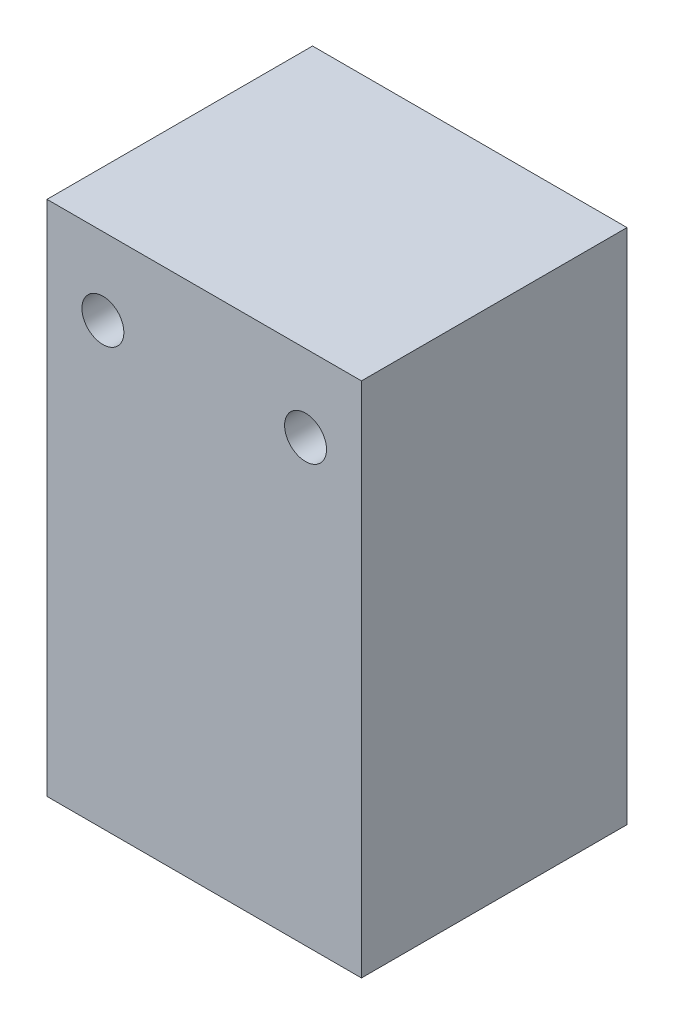
SolidWorks part; units mm, degrees
ref_plane "Front Plane" through (0, 0, 0) normal (0, 0, 1) x (1, 0, 0)
ref_plane "Top Plane" through (0, 0, 0) normal (0, 1, 0) x (1, 0, 0)
ref_plane "Right Plane" through (0, 0, 0) normal (1, 0, 0) x (0, 0, -1)
sketch "Sketch1" plane through (0, 0, 0) normal (0, 0, 1) x (1, 0, 0)
  line L0 (-11.25, 8.7) -> (-11.25, 0) construction
  line L1 (0, 0) -> (-22.5, 0)
  line L2 (0, 0) -> (0, 37)
  line L3 (0, 37) -> (-22.5, 37)
  line L4 (-22.5, 0) -> (-22.5, 37)
  line L5 (-13.0815, 8.7) -> (-9.4185, 8.7)
  line L7 (-13.0815, 12.4) -> (-9.4185, 12.4)
  circle A0 centre (-4, 31.5) radius 1.5
  circle A1 centre (-18.5, 31.5) radius 1.5
  arc A2 (-13.0815, 8.7) -> (-13.0815, 12.4) centre (-11.4, 10.55) cw
  arc A4 (-9.4185, 12.4) -> (-9.4185, 8.7) centre (-11.1, 10.55) cw
  point P15 (-8.6, 10.55)
  point P16 (-13.9, 10.55)
  point P17 (-13.9268, 6.3824)
  point P18 (-14.6939, 8.1532)
  point P19 (-10.077, 4.2294)
  point P20 (0, 0)
  point P21 (-11.4, 5.0614)
  dimension "D2" = 3
  dimension "D8" = 2.5
  dimension "D9" = 5.3
  dimension "D10" = 8.7
  dimension "D1" = 31.5
  dimension "D3" = 4
  dimension "D4" = 4
  dimension "D5" = 22.5
  dimension "D6" = 37
  dimension "D7" = 3.7
extrude "Boss-Extrude1" add sketch "Sketch1" along normal blind 19 contours L7 A4 L5 L1 L2 L3 L4 A2 A1 A0 | A4 L7 A2 L5 region at (-11.25, 18.4467, 0) region at (-11.25, 10.55, 0)
extrude "Boss-Extrude2" add sketch "Sketch1<3>" against normal blind 8 contours A4 L7 A2 L5 region at (-11.25, 10.55, 0)
sketch "Sketch1<3>" plane through (0, 0, 0) normal (0, 0, 1) x (1, 0, 0) same geometry as "Sketch1"
sketch "Sketch2" plane through (0, 0, 0) normal (0, -1, 0) x (1, 0, 0)
  line L0 (-11.25, 8.15) -> (-11.25, 0) construction
  line L1 (-13.825, 10.85) -> (-8.675, 10.85)
  line L2 (-13.825, 10.85) -> (-13.825, 8.15)
  line L3 (-13.825, 8.15) -> (-8.675, 8.15)
  line L4 (-8.675, 10.85) -> (-8.675, 8.15)
  line L5 (0, 0) -> (-22.5, 0) construction
  line L6 (-11.25, 10.85) -> (-11.25, 19) construction
  line L7 (0, 19) -> (-22.5, 19) construction
  dimension "D1" = 2.7
  dimension "D2" = 5.15
extrude "Boss-Extrude3" add sketch "Sketch2" along normal blind 4.8
sketch "Sketch3" plane through (0, 0, 8.15) normal (0, 0, -1) x (-1, 0, 0)
  line L0 (11.25, -2.4) -> (11.25, 0) construction
  line L1 (0, 0) -> (22.5, 0) construction
  line L2 (11.25, -2.4) -> (13.825, -2.4) construction
  line L3 (13.825, -4.8) -> (13.825, 0) construction
  circle A0 centre (11.25, -2.4) radius 1.5
  dimension "D1" = 3
extrude "Cut-Extrude1" cut sketch "Sketch3" against normal through all both and the other way through all
